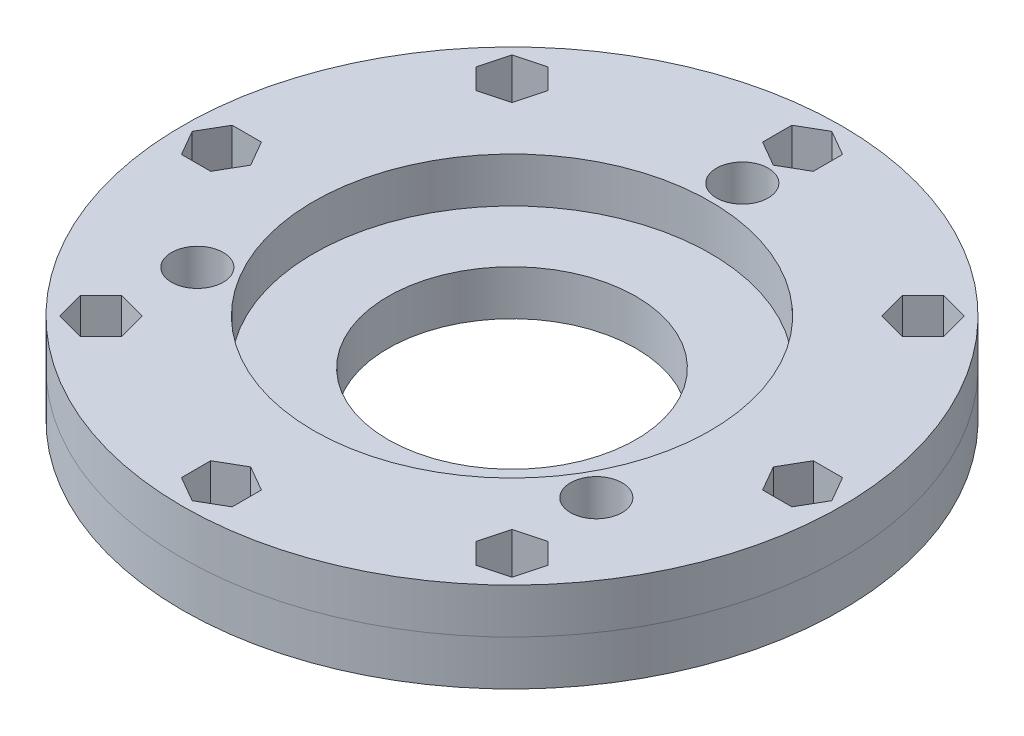
SolidWorks part; units mm, degrees
ref_plane "Front Plane" through (0, 0, 0) normal (0, 0, 1) x (1, 0, 0)
ref_plane "Top Plane" through (0, 0, 0) normal (0, 1, 0) x (1, 0, 0)
ref_plane "Right Plane" through (0, 0, 0) normal (1, 0, 0) x (0, 0, -1)
sketch "Sketch1" plane through (0, 0, 0) normal (0, 1, 0) x (1, 0, 0)
  circle A0 centre (0, 0) radius 46.5
  circle A1 centre (0, 0) radius 32.5 construction
  circle A2 centre (0, 32.5) radius 2.5
  circle A3 centre (28.1458, -16.25) radius 2.5
  circle A4 centre (-28.1458, -16.25) radius 2.5
  circle A5 centre (0, 0) radius 17.5
  point P13 (0, 0)
  dimension "D1" = 93
  dimension "D2" = 65
  dimension "D3" = 5
  dimension "D5" = 35
  dimension "D4" = 3
extrude "Boss-Extrude1" add sketch "Sketch1" along normal blind 12.7
sketch "Sketch2" plane through (0, 12.7, 0) normal (0, 1, 0) x (1, 0, 0)
  circle A0 centre (0, 0) radius 28
  dimension "D1" = 56
extrude "Cut-Extrude1" cut sketch "Sketch2" against normal blind 6.35
sketch "Sketch3" plane through (0, 12.7, 0) normal (0, 1, 0) x (1, 0, 0)
  line L0 (0, 41) -> (0, 0) construction
  circle A0 centre (0, 0) radius 41 construction
  circle A1 centre (0, 41) radius 2.5
  circle A2 centre (28.9914, 28.9914) radius 2.5
  circle A3 centre (41, 0) radius 2.5
  circle A4 centre (28.9914, -28.9914) radius 2.5
  circle A5 centre (0, -41) radius 2.5
  circle A6 centre (-28.9914, -28.9914) radius 2.5
  circle A7 centre (-41, 0) radius 2.5
  circle A8 centre (-28.9914, 28.9914) radius 2.5
  point P21 (0, 0)
  dimension "D1" = 82
  dimension "D2" = 5
  dimension "D3" = 8
extrude "Cut-Extrude2" cut sketch "Sketch3" against normal blind 6.35
sketch "Sketch4" plane through (0, 12.7, 0) normal (0, 1, 0) x (1, 0, 0)
  line L0 (0, 45.1281) -> (-3.575, 43.064)
  line L1 (-3.575, 43.064) -> (-3.575, 38.936)
  line L2 (-3.575, 38.936) -> (0, 36.8719)
  line L3 (0, 36.8719) -> (3.575, 38.936)
  line L4 (3.575, 38.936) -> (3.575, 43.064)
  line L5 (3.575, 43.064) -> (0, 45.1281)
  line L6 (0, 45.1281) -> (0, 36.8719) construction
  line L7 (32.9788, 27.923) -> (31.9104, 31.9104)
  line L8 (31.9104, 31.9104) -> (27.923, 32.9788)
  line L9 (27.923, 32.9788) -> (25.004, 30.0598)
  line L10 (25.004, 30.0598) -> (26.0724, 26.0724)
  line L11 (26.0724, 26.0724) -> (30.0598, 25.004)
  line L12 (30.0598, 25.004) -> (32.9788, 27.923)
  line L13 (43.064, -3.575) -> (45.1281, 0)
  line L14 (45.1281, 0) -> (43.064, 3.575)
  line L15 (43.064, 3.575) -> (38.936, 3.575)
  line L16 (38.936, 3.575) -> (36.8719, 0)
  line L17 (36.8719, 0) -> (38.936, -3.575)
  line L18 (38.936, -3.575) -> (43.064, -3.575)
  line L19 (27.923, -32.9788) -> (31.9104, -31.9104)
  line L20 (31.9104, -31.9104) -> (32.9788, -27.923)
  line L21 (32.9788, -27.923) -> (30.0598, -25.004)
  line L22 (30.0598, -25.004) -> (26.0724, -26.0724)
  line L23 (26.0724, -26.0724) -> (25.004, -30.0598)
  line L24 (25.004, -30.0598) -> (27.923, -32.9788)
  line L25 (-3.575, -43.064) -> (0, -45.1281)
  line L26 (0, -45.1281) -> (3.575, -43.064)
  line L27 (3.575, -43.064) -> (3.575, -38.936)
  line L28 (3.575, -38.936) -> (0, -36.8719)
  line L29 (0, -36.8719) -> (-3.575, -38.936)
  line L30 (-3.575, -38.936) -> (-3.575, -43.064)
  line L31 (-32.9788, -27.923) -> (-31.9104, -31.9104)
  line L32 (-31.9104, -31.9104) -> (-27.923, -32.9788)
  line L33 (-27.923, -32.9788) -> (-25.004, -30.0598)
  line L34 (-25.004, -30.0598) -> (-26.0724, -26.0724)
  line L35 (-26.0724, -26.0724) -> (-30.0598, -25.004)
  line L36 (-30.0598, -25.004) -> (-32.9788, -27.923)
  line L37 (-43.064, 3.575) -> (-45.1281, 0)
  line L38 (-45.1281, 0) -> (-43.064, -3.575)
  line L39 (-43.064, -3.575) -> (-38.936, -3.575)
  line L40 (-38.936, -3.575) -> (-36.8719, 0)
  line L41 (-36.8719, 0) -> (-38.936, 3.575)
  line L42 (-38.936, 3.575) -> (-43.064, 3.575)
  line L43 (-27.923, 32.9788) -> (-31.9104, 31.9104)
  line L44 (-31.9104, 31.9104) -> (-32.9788, 27.923)
  line L45 (-32.9788, 27.923) -> (-30.0598, 25.004)
  line L46 (-30.0598, 25.004) -> (-26.0724, 26.0724)
  line L47 (-26.0724, 26.0724) -> (-25.004, 30.0598)
  line L48 (-25.004, 30.0598) -> (-27.923, 32.9788)
  line L49 (-30.0598, 25.004) -> (-27.923, 32.9788) construction
  circle A0 centre (0, 32.5) radius 3.65
  circle A1 centre (28.1458, -16.25) radius 3.65
  circle A2 centre (-28.1458, -16.25) radius 3.65
  circle A3 centre (-28.1458, -16.25) radius 2.5 construction
  circle A4 centre (0, 41) radius 2.5 construction
  circle A5 centre (0, 41) radius 2.5 construction
  circle A6 centre (-28.9914, 28.9914) radius 2.5 construction
  circle A7 centre (-28.9914, 28.9914) radius 2.5 construction
  point P9 (0, 0)
  point P64 (0, 0)
  dimension "D1" = 3
  dimension "8" = 7.3
  dimension "7.15" = 7.15
  dimension "D3" = 120
  dimension "D4" = 120
  dimension "D5" = 8
extrude "Cut-Extrude3" cut sketch "Sketch4" against normal blind 6.35
sketch "Sketch5" plane through (0, 12.7, 0) normal (0, 1, 0) x (1, 0, 0)
  line L2 (0, 36.8719) -> (0, 45.1281) construction
  circle A0 centre (0, 41) radius 2.5 construction
  circle A1 centre (0, 32.5) radius 2.5 construction
  circle A2 centre (0, 32.5) radius 2.5 construction
  dimension "D1" = 5
split "Split1" bodies to split 105 resulting bodies 106 107 split by face at (0, 6.35, 17.5)
